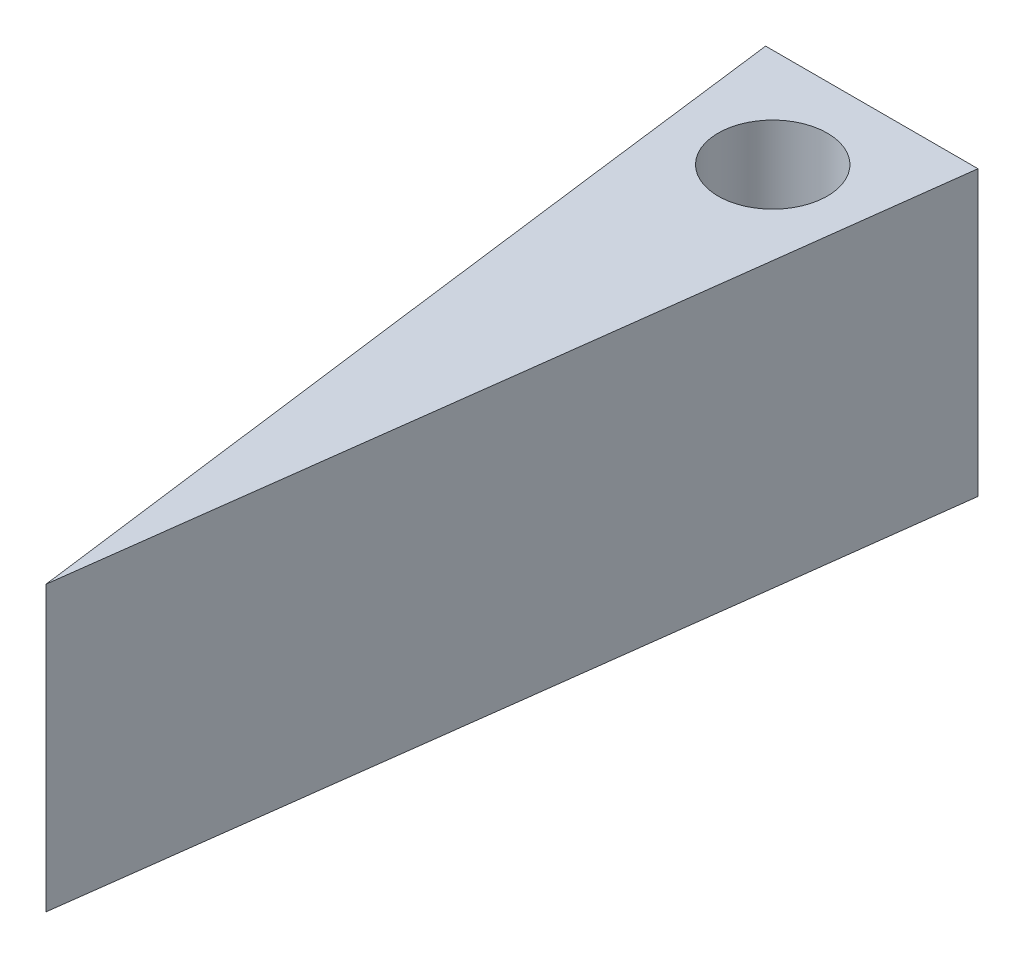
SolidWorks part; units mm, degrees
ref_plane "Front Plane" through (0, 0, 0) normal (0, 0, 1) x (1, 0, 0)
ref_plane "Top Plane" through (0, 0, 0) normal (0, 1, 0) x (1, 0, 0)
ref_plane "Right Plane" through (0, 0, 0) normal (1, 0, 0) x (0, 0, -1)
sketch "Sketch1" plane through (0, 0, 0) normal (0, 1, 0) x (1, 0, 0)
  line L0 (1.1081, 1.7265) -> (-45.0799, 1.7265) construction
  line L1 (-45.0799, 1.7265) -> (-45.0799, -11.2275) construction
  line L2 (-45.0799, -11.2275) -> (43.7517, -11.2275) construction
  line L3 (1.1081, 103.3269) -> (1.1081, -99.8738) construction
  line L4 (-45.0799, -11.2275) -> (-45.0799, -20.7525) construction
  line L5 (-28.2049, 1.7265) -> (-28.2049, -3.6075) construction
  line L6 (-9.9553, -3.6075) -> (-6.7697, -3.6075)
  line L7 (-28.2049, -3.6075) -> (-9.9553, -3.6075) construction
  line L8 (-6.7697, -3.6075) -> (1.1081, -3.6075) construction
  line L9 (8.9859, -3.6075) -> (12.1715, -3.6075)
  line L10 (12.1715, -3.6075) -> (18.1346, -3.6075) construction
  line L11 (12.1715, -3.6075) -> (18.1346, -3.6075) construction
  line L12 (18.1346, -3.6075) -> (29.3788, -3.6075) construction
  line L13 (1.1081, -3.6075) -> (8.9859, -3.6075) construction
  line L14 (-6.7697, -3.6075) -> (8.9859, -3.6075)
  circle A0 centre (1.1081, -11.3265) radius 1.9844 construction
  circle A1 centre (1.1081, -11.3265) radius 1.9844
  spline S0 degree 3 poles (1.1081, -99.8738) (4.5273, -73.5318) (7.9866, -47.1872) (10.6029, -20.7525) knots 0 0 0 0 0.38497 0.38497 0.38497 0.38497
  spline S3 degree 3 poles (1.1081, -99.8738) (-2.3112, -73.5318) (-5.7704, -47.1872) (-8.3867, -20.7525) knots 0 0 0 0 0.38497 0.38497 0.38497 0.38497
  spline S4 degree 3 poles (10.6029, -20.7525) (11.1, -15.7302) (11.6306, -10.016) (12.114, -4.2968) (12.1715, -3.6075) knots 0.38497 0.38497 0.38497 0.38497 0.458109 0.468132 0.468132 0.468132 0.468132
  spline S5 degree 3 poles (-8.3867, -20.7525) (-8.8838, -15.7302) (-9.4144, -10.016) (-9.8978, -4.2968) (-9.9553, -3.6075) knots 0.38497 0.38497 0.38497 0.38497 0.458109 0.468132 0.468132 0.468132 0.468132
  spline S8 degree 3 poles (12.1715, -3.6075) (12.8364, 4.367) (14.1908, 23.6726) (14.0058, 48.0803) (13.0188, 67.5796) (11.3266, 78.9472) (9.5869, 86.9693) (8.1237, 93.6397) (6.4505, 97.563) (4.8164, 101.3994) (2.3437, 102.5279) (1.1081, 103.3269) knots 0.468132 0.468132 0.468132 0.468132 0.584075 0.748482 0.821537 0.866809 0.914778 0.94069 0.965303 0.976863 1 1 1 1 construction
  spline S9 degree 3 poles (1.1081, 99.6196) (1.2739, 99.518) (1.6209, 99.2976) (2.0134, 99.0137) (2.3095, 98.7539) (2.4667, 98.5788) (2.6076, 98.3713) (2.8163, 97.9774) (3.0534, 97.4394) (3.4327, 96.5453) (3.8774, 95.496) (4.541, 93.8448) (5.2023, 91.9048) (5.8236, 89.3366) (6.4213, 86.5662) (7.0145, 83.8293) (7.767, 80.1951) (8.6007, 75.6781) (9.6391, 68.4081) (10.3034, 59.2354) (10.6788, 47.9926) (10.8555, 36.7918) (10.7415, 25.5951) (10.3009, 14.4244) (9.6564, 4.6878) (9.1767, -1.3266) (8.9859, -3.6075) knots 0.118744 0.118744 0.118744 0.118744 0.122149 0.125554 0.12896 0.132365 0.13577 0.139175 0.142581 0.145986 0.152796 0.159607 0.173228 0.186849 0.20047 0.214091 0.227711 0.254953 0.282195 0.336679 0.391163 0.445646 0.50013 0.554614 0.609098 0.642376 0.642376 0.642376 0.642376 construction
  spline S10 degree 3 poles (-7.1984, 1.7265) (-7.237, 2.2289) (-7.5577, 6.4638) (-8.0847, 14.4244) (-8.5253, 25.5951) (-8.6393, 36.7918) (-8.4626, 47.9926) (-8.0872, 59.2354) (-7.4229, 68.4081) (-6.3845, 75.6781) (-5.5508, 80.1951) (-4.7983, 83.8293) (-4.2051, 86.5662) (-3.6074, 89.3366) (-2.9861, 91.9048) (-2.3248, 93.8448) (-1.6612, 95.496) (-1.2165, 96.5453) (-0.8372, 97.4394) (-0.6001, 97.9774) (-0.3914, 98.3713) (-0.2505, 98.5788) (-0.0933, 98.7539) (0.2028, 99.0137) (0.5953, 99.2976) (0.9423, 99.518) (1.1081, 99.6196) knots 0.492798 0.492798 0.492798 0.492798 0.50013 0.554614 0.609098 0.663581 0.718065 0.772549 0.827033 0.854275 0.881516 0.895137 0.908758 0.922379 0.936 0.949621 0.956432 0.963242 0.966647 0.970053 0.973458 0.976863 0.980268 0.983674 0.987079 0.990484 0.990484 0.990484 0.990484 construction
  spline S11 degree 3 poles (-10.3826, 1.7265) (-10.8572, 7.9268) (-11.9611, 25.4575) (-11.7896, 48.0803) (-10.8026, 67.5796) (-9.1104, 78.9472) (-7.3707, 86.9693) (-5.9075, 93.6397) (-4.2343, 97.563) (-2.6002, 101.3994) (-0.1276, 102.5279) (1.1081, 103.3269) knots 0.493976 0.493976 0.493976 0.493976 0.584075 0.748482 0.821537 0.866809 0.914778 0.94069 0.965303 0.976863 1 1 1 1 construction
  spline S12 degree 3 poles (-9.9553, -3.6075) (-10.1035, -1.8299) (-10.2465, -0.0519) (-10.3826, 1.7265) knots 0.468132 0.468132 0.468132 0.468132 0.493976 0.493976 0.493976 0.493976 construction
  spline S13 degree 3 poles (-6.7697, -3.6075) (-6.9185, -1.8292) (-7.0618, -0.0511) (-7.1984, 1.7265) knots 0.466852 0.466852 0.466852 0.466852 0.492798 0.492798 0.492798 0.492798 construction
  dimension "D4" = 3.9688
  dimension "D1" = 12.954
  dimension "D2" = 9.525
  dimension "D3" = 5.334
extrude "Boss-Extrude1" add sketch "Sketch1" along normal blind 169.8727
sketch "Sketch2" plane through (0, 169.8727, 0) normal (0, 1, 0) x (1, 0, 0)
  line L1 (-9.9553, -3.6075) -> (25.8085, -3.6075)
  line L2 (-9.9553, -3.6075) -> (-9.9553, -26.3125)
  line L3 (-9.9553, -26.3125) -> (25.8085, -26.3125)
  line L4 (25.8085, -3.6075) -> (25.8085, -26.3125)
  circle A0 centre (1.1081, -11.3265) radius 1.9844 construction
  dimension "D1" = 14.986
extrude "Cut-Extrude1" cut sketch "Sketch2" against normal blind 23.0581
extrude "Cut-Extrude2" cut sketch "Sketch2<2>" along normal blind 23.0581 from surface starting at face at (-1.1046, 0, 29.7187)
sketch "Sketch2<2>" plane through (0, 169.8727, 0) normal (0, 1, 0) x (1, 0, 0) same geometry as "Sketch2"
fillet "Fillet1" radius 7.62 6 edges at (-7.8242, 11.5291, 26.3125) (10.0403, 11.5291, 26.3125) (12.1715, 84.9363, 3.6075) (-7.8242, 158.3436, 26.3125) (10.0403, 158.3436, 26.3125)
sketch "Sketch6" plane through (0, 0, 0) normal (0, -1, 0) x (1, 0, 0)
  line L0 (1.1081, 3.6075) -> (1.1081, 99.8738) construction
  line L1 (-1.6395, 3.6075) -> (3.8557, 3.6075) construction
  line L2 (-6.9254, 34.7606) -> (9.1416, 34.7606) construction
  circle A0 centre (1.1081, 71.9338) radius 2.1
  circle A1 centre (1.1081, 34.7606) radius 2.1
  dimension "D1" = 4.2
  dimension "D2" = 27.94
extrude "Cut-Extrude3" cut sketch "Sketch6" against normal through all both and the other way through all
sketch "Sketch7" plane through (0, 0, 0) normal (1, 0, 0) x (0, 0, -1)
  line L0 (-3.6075, 146.8145) -> (-3.6075, 23.0581) construction
  line L1 (-99.8738, 0) -> (-3.6075, 0)
  line L2 (-99.8738, 0) -> (-99.8738, 154.1951)
  line L3 (-99.8738, 154.1951) -> (-3.6075, 154.1951)
  line L4 (-3.6075, 0) -> (-3.6075, 154.1951)
  line L6 (-99.8738, 169.8727) -> (-3.6075, 169.8727)
  line L7 (-99.8738, 169.8727) -> (-99.8738, 165.1069)
  line L8 (-99.8738, 165.1069) -> (-3.6075, 165.1069)
  line L9 (-3.6075, 169.8727) -> (-3.6075, 165.1069)
  dimension "D2" = 10.9118
extrude "Cut-Extrude4" cut sketch "Sketch7" against normal through all both and the other way through all
sketch "Sketch8" plane through (0, 154.1951, 0) normal (0, -1, 0) x (1, 0, 0)
  line L1 (-35.7382, 68.1238) -> (19.5961, 68.1238)
  line L2 (-35.7382, 68.1238) -> (-35.7382, 26.3125)
  line L3 (-35.7382, 26.3125) -> (19.5961, 26.3125)
  line L4 (19.5961, 68.1238) -> (19.5961, 26.3125)
  dimension "D1" = 0
  dimension "D2" = 31.75
extrude "Cut-Extrude5" cut sketch "Sketch8" against normal through all both
